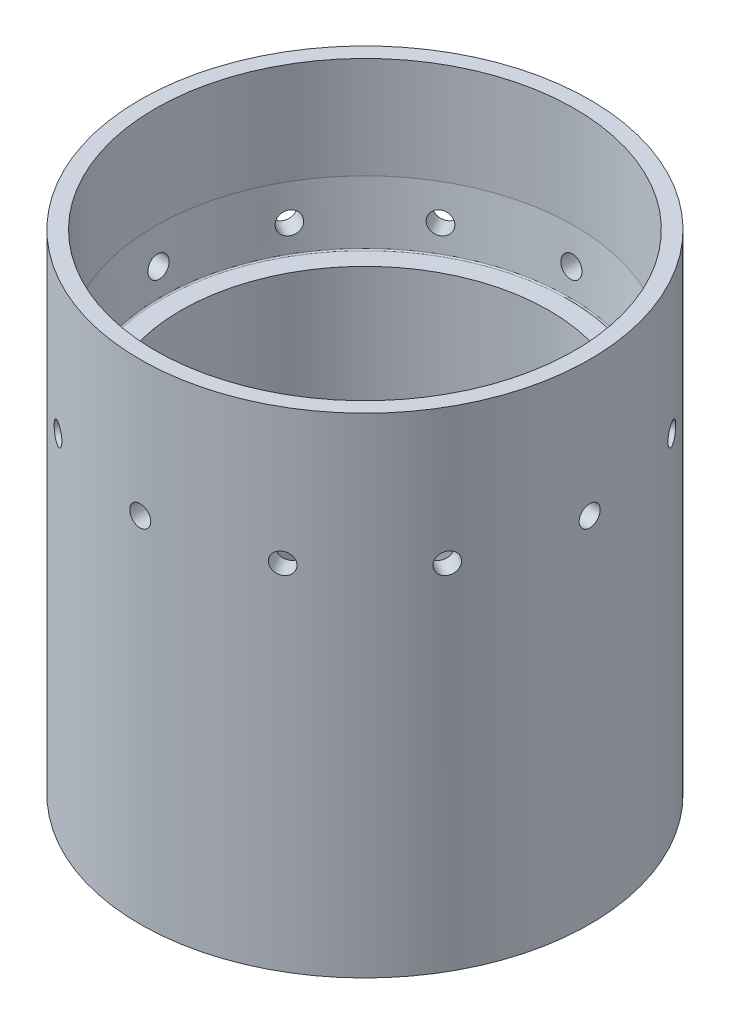
SolidWorks part; units mm, degrees
material "AISI 304"
ref_plane "Front Plane" through (0, 0, 0) normal (0, 0, 1) x (1, 0, 0)
ref_plane "Top Plane" through (0, 0, 0) normal (0, 1, 0) x (1, 0, 0)
ref_plane "Right Plane" through (0, 0, 0) normal (1, 0, 0) x (0, 0, -1)
sketch "Sketch2" plane through (0, 0, 0) normal (0, 0, 1) x (1, 0, 0)
  line L4 (0, 0) -> (0, -101.6) construction
  line L6 (57.15, 0) -> (63.4619, 0)
  line L7 (57.15, 0) -> (57.15, -101.6)
  line L8 (57.15, -101.6) -> (69.85, -101.6)
  line L9 (69.85, 50.292) -> (69.85, -101.6)
  line L11 (65.1002, 18.7259) -> (63.4619, 0)
  line L12 (65.1002, 18.7259) -> (65.1002, 50.292)
  line L13 (65.1002, 50.292) -> (69.85, 50.292)
  dimension "D2" = 114.3
  dimension "D3" = 12.7
  dimension "D4" = 101.6
  dimension "D1" = 6.3119
  dimension "D6" = 5
  dimension "D5" = 50.292
  dimension "D7" = 130.2004
revolve "Revolve1" add sketch "Sketch2" angle 360 about L4
fillet "Tool Radius" radius 0.4064 2 edges at (-65.1002, 18.7259, 0) (-63.4619, 0, 0)
ref_plane "Plane1" through (0, 0, 69.85) normal (0, 0, 1) x (1, 0, 0)
sketch "Sketch3" plane through (0, 0, 69.85) normal (0, 0, 1) x (1, 0, 0)
  line L0 (57.15, 0) -> (-57.15, 0) construction
  point P0 (0, 8.255)
  dimension "D1" = 8.255
hole_wizard "F (0.257) Diameter Hole1" positions "Sketch3" profile "Sketch4" hole size "F" standard "ANSI Inch" end condition up to next
sketch "Sketch4" plane through (0, 8.255, 69.85) normal (1, 0, 0) x (0, -1, 0)
  line L0 (0, 0) -> (0, 5.6659)
  line L1 (0, 5.6659) -> (3.2639, 5.6659)
  line L2 (3.2639, 5.6659) -> (3.2639, 0)
  line L5 (3.2639, 0) -> (0, 0)
  line L11 (0, -6.35) -> (0, 107.95) construction
  dimension "Thru Hole Dia." = 6.5278
  dimension "Thru Hole Depth" = 5.6659
sketch "Sketch5" plane through (0, -101.6, 0) normal (0, -1, 0) x (1, 0, 0)
  line L0 (0, 64.77) -> (-61.5999, 20.015) construction
  line L1 (-61.5999, 20.015) -> (-38.0709, -52.4) construction
  line L2 (-38.0709, -52.4) -> (38.0709, -52.4) construction
  line L3 (38.0709, -52.4) -> (61.5999, 20.015) construction
  line L4 (61.5999, 20.015) -> (0, 64.77) construction
  circle A0 centre (0, 0) radius 69.85 construction
  circle A1 centre (0, 0) radius 64.77 construction
  point P0 (0, 64.77)
  point P8 (61.5999, 20.015)
  point P10 (38.0709, -52.4)
  point P12 (-38.0709, -52.4)
  point P14 (-61.5999, 20.015)
  dimension "D1" = 5.08
hole_wizard "1/4-20 Tapped Hole1" positions "Sketch5" profile "Sketch6" tap size "1/4-20" standard "ANSI Inch"
sketch "Sketch6" plane through (0, -101.6, 64.77) normal (1, 0, 0) x (0, 0, -1)
  line L0 (0, 0) -> (0, 22.4888)
  line L1 (0, 22.4888) -> (2.5527, 20.955)
  line L2 (2.5527, 20.955) -> (2.5527, 0)
  line L5 (2.5527, 0) -> (0, 0)
  line L10 (0, 22.4888) -> (-2.5527, 20.955) construction
  line L11 (0, -6.35) -> (0, 107.95) construction
  dimension "Tap Drill Dia." = 5.1054
  dimension "Tap Drill Depth" = 20.955
  dimension "Drill Angle" = 118
cosmetic thread "Hole Thread1" parameters "D1"=15.875, "D2"=6.35
cosmetic thread "Hole Thread7" parameters "D1"=15.875, "D2"=6.35
cosmetic thread "Hole Thread8" parameters "D1"=15.875, "D2"=6.35
cosmetic thread "Hole Thread9" parameters "D1"=15.875, "D2"=6.35
cosmetic thread "Hole Thread10" parameters "D1"=15.875, "D2"=6.35
pattern_circular "CirPattern1" count 12 over 360 about axis through (0, 0, 0) along (0, 1, 0) of "F (0.257) Diameter Hole1" reverse direction yes
cosmetic thread "Hole Thread2" parameters "D1"=15.875, "D2"=6.35
cosmetic thread "Hole Thread3" parameters "D1"=15.875, "D2"=6.35
cosmetic thread "Hole Thread4" parameters "D1"=15.875, "D2"=6.35
cosmetic thread "Hole Thread5" parameters "D1"=15.875, "D2"=6.35
cosmetic thread "Hole Thread6" parameters "D1"=15.875, "D2"=6.35
equation "\"length\"=4"
equation "\"wallThickness\"=0.5"
equation "\"chamberID\"= 4.5"
equation "\"D2@Sketch2\"=\"chamberID\""
